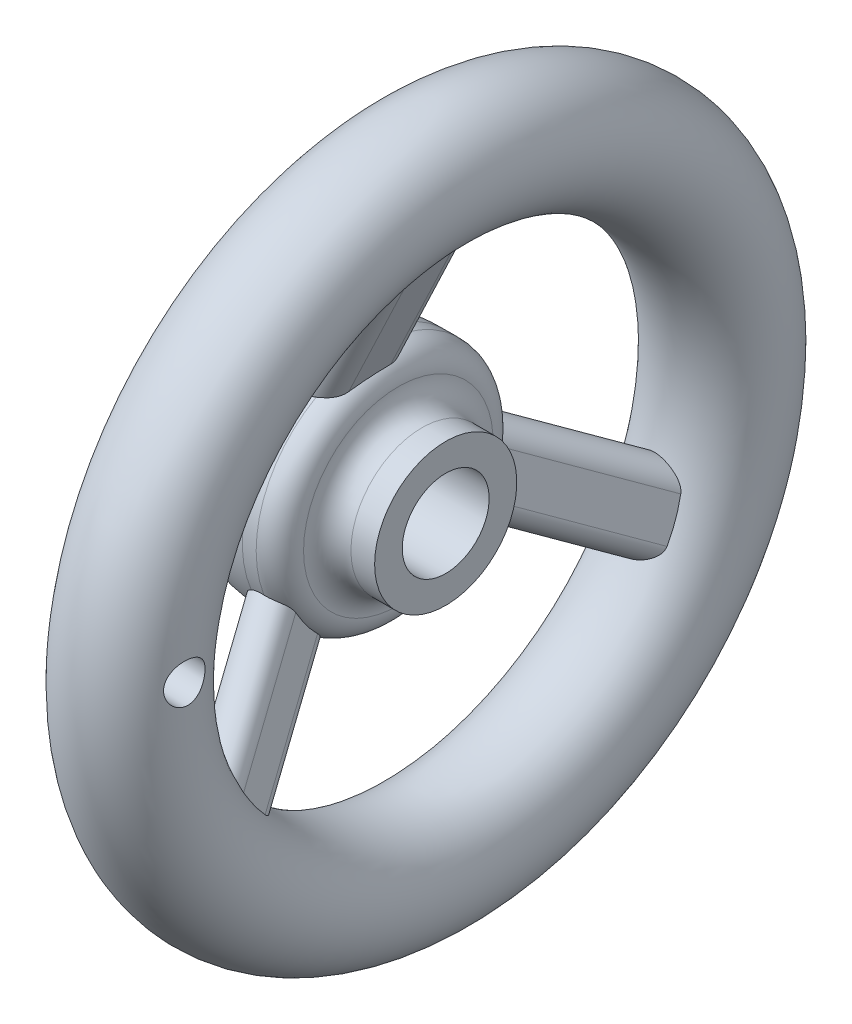
SolidWorks part; units mm, degrees
ref_plane "Front Plane" through (0, 0, 0) normal (0, 0, 1) x (1, 0, 0)
ref_plane "Top Plane" through (0, 0, 0) normal (0, 1, 0) x (1, 0, 0)
ref_plane "Right Plane" through (0, 0, 0) normal (1, 0, 0) x (0, 0, -1)
sketch "Sketch1" plane through (0, 0, 0) normal (0, 0, 1) x (1, 0, 0)
  line L0 (0, 0) -> (158.2928, 0) construction
  line L1 (0, 5.5) -> (24.0265, 5.5)
  line L2 (24.0265, 5.5) -> (24.0265, 9)
  line L3 (24.0265, 9) -> (21.0265, 9)
  line L4 (15.0265, 15) -> (13.2665, 15)
  line L5 (0, 5.5) -> (0, 11)
  arc A0 (21.0265, 9) -> (18.0265, 12) centre (21.0265, 12) cw
  arc A1 (18.0265, 12) -> (15.0265, 15) centre (15.0265, 12) ccw
  arc A2 (0, 11) -> (13.2665, 15) centre (13.2665, -9) cw
  point P14 (24.0265, 7.25)
  dimension "D5" = 3
  dimension "D6" = 3
  dimension "D8" = 24
  dimension "D1" = 90
  dimension "D2" = 5.5
  dimension "D3" = 9
  dimension "D4" = 3
  dimension "D7" = 11
  dimension "D9" = 24.0265
  dimension "D10" = 15
revolve "Revolve1" add sketch "Sketch1" angle 360 about L0
sketch "Sketch2" plane through (0, 0, 0) normal (0, 0, 1) x (1, 0, 0)
  line L0 (29.0265, 37.5) -> (29.0265, 14.9726) construction
  line L1 (24.0265, -9) -> (24.0265, 9) construction
  line L2 (0, 0) -> (61.9588, 0) construction
  circle A0 centre (21.5265, 37.5) radius 7.5
  dimension "D1" = 15
  dimension "D2" = 5
  dimension "D3" = 37.5
revolve "Revolve2" add sketch "Sketch2" angle 360 about L2
sketch "Sketch3" plane through (0, 0, 0) normal (0, 0, 1) x (1, 0, 0)
  line L0 (27.7161, 41.7354) -> (15.0265, 15)
  arc A0 (29.0265, 37.5) -> (14.0265, 37.5) centre (21.5265, 37.5) ccw construction
ref_plane "Plane1" through (15.0265, 15, 0) normal (-0.4288, -0.9034, 0) x (-0.9034, 0.4288, 0)
sketch "Sketch4" plane through (15.0265, 15, 0) normal (-0.4288, -0.9034, 0) x (-0.9034, 0.4288, 0)
  line L0 (0.1617, -5.1173) -> (0.1617, -0.1173) construction
  line L1 (-2.3383, -5.1173) -> (-2.3383, -0.1173)
  line L2 (2.6617, -5.1173) -> (2.6617, -0.1173)
  arc A0 (-2.3383, -5.1173) -> (2.6617, -5.1173) centre (0.1617, -5.1173) ccw
  arc A1 (2.6617, -0.1173) -> (-2.3383, -0.1173) centre (0.1617, -0.1173) ccw
  point P2 (0.1617, -2.6173)
  dimension "D2" = 2.5
  dimension "D1" = 5
extrude "Boss-Extrude1" add sketch "Sketch4" along normal up to next and the other way up to next
pattern_circular "CirPattern1" count 3 over 360 about axis through (0, 0, 0) along (1, 0, 0) of "Boss-Extrude1"
sketch "Sketch5" plane through (0, 0, 0) normal (0, 1, 0) x (1, 0, 0)
  line L0 (24.0265, -9) -> (24.0265, 9) construction
  circle A0 centre (4.0265, 0) radius 2
  dimension "D1" = 4
  dimension "D2" = 20
extrude "Cut-Extrude1" cut sketch "Sketch5" against normal mid plane 36
hole_wizard "M6x1.0 Tapped Hole1" positions "3DSketch1" profile "Sketch6" tap size "M6x1.0" standard "ANSI Metric"
sketch3d "3DSketch1"
  point P0 (29.0167, 3.8714, 37.6857)
sketch "Sketch6" plane through (29.0167, 3.8714, 37.6857) normal (-0.0397, 0.7065, 0.7065) x (0.0323, 0.7076, -0.7058)
  line L0 (0, 0) -> (0, 8.5022)
  line L1 (0, 8.5022) -> (2.5, 7)
  line L2 (2.5, 7) -> (2.5, 0)
  line L5 (2.5, 0) -> (0, 0)
  line L10 (0, 8.5022) -> (-2.5, 7) construction
  line L11 (0, -6.35) -> (0, 107.95) construction
  dimension "Tap Drill Dia." = 5
  dimension "Tap Drill Depth" = 7
  dimension "Drill Angle" = 118
cosmetic thread "Hole Thread1" parameters "D1"=6, "D2"=6
